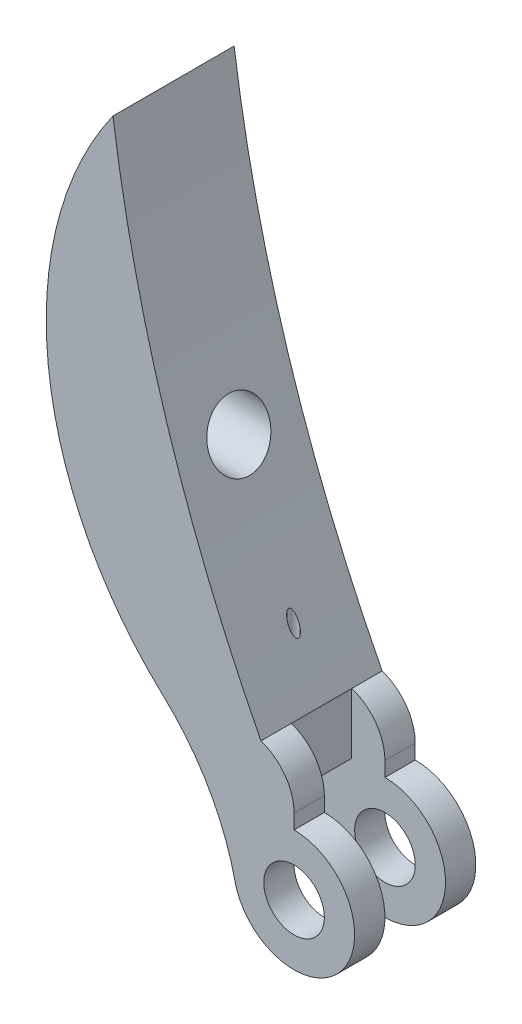
SolidWorks part; units mm, degrees
ref_plane "前视基准面" through (0, 0, 0) normal (0, 0, 1) x (1, 0, 0)
ref_plane "上视基准面" through (0, 0, 0) normal (0, 1, 0) x (1, 0, 0)
ref_plane "右视基准面" through (0, 0, 0) normal (1, 0, 0) x (0, 0, -1)
other "Configuration Table"
sketch "Sketch1" plane through (0, 0, 0) normal (0, 0, 1) x (1, 0, 0)
  line L0 (-2.5, 0) -> (-2.5, 5)
  line L1 (0, 0) -> (0, 5)
  line L2 (0, 5) -> (-2.5, 5)
  circle A0 centre (0, 0) radius 2.5
  circle A1 centre (0, 0) radius 1.25
  dimension "D1" = 2.5
  dimension "D2" = 5
  dimension "D3" = 5
extrude "Boss-Extrude1" add sketch "Sketch1" along normal blind 5 contours A0 L1 L2 L0 | A1 A0 region at (-1.7178, 1.7178, 0) region at (-1.3722, 3.4305, 0)
sketch "Sketch2" plane through (0, 0, 5) normal (0, 0, 1) x (1, 0, 0)
  line L0 (0, 2.5) -> (-2.5, 2.5) construction
  line L1 (0, 2.5) -> (0, 5) construction
  line L2 (-2.5, 0) -> (-2.5, 5) construction
  line L3 (0, 2.5) -> (4.7745, 15.618) construction
  line L4 (0, 2.5) -> (51.9615, 32.5) construction
  line L5 (0, 5) -> (0, 2.5) construction
  line L6 (-2.5, 2.5) -> (0, 2.5)
  arc A1 (-2.5, 0) -> (0, 2.5) centre (0, 0) ccw construction
  arc A2 (-2.5, 2.5) -> (-7.4726, 24.2787) centre (4.7745, 15.618) cw
  arc A3 (-7.4726, 24.2787) -> (0, 2.5) centre (51.9615, 32.5) ccw
  dimension "D1" = 60
  dimension "D2" = 15
  dimension "D3" = 20
  dimension "D4" = 40
extrude "Boss-Extrude2" add sketch "Sketch2" against normal blind 5
fillet "Fillet2" radius 10 1 edges at (-2.5, 2.5, 2.5)
sketch "Sketch4" plane through (0, 0, 0) normal (1, 0, 0) x (0, 0, -1)
  line L0 (-2.5, 5) -> (-2.5, 0) construction
  line L1 (-5, 5) -> (0, 5) construction
  line L3 (-3.75, -2.5) -> (-1.25, -2.5)
  line L4 (-3.75, -2.5) -> (-3.75, 2.5)
  line L5 (-3.75, 2.5) -> (-1.25, 2.5)
  line L6 (-1.25, -2.5) -> (-1.25, 2.5)
  line L7 (-3.75, -2.5) -> (-1.25, 2.5) construction
  line L8 (-3.75, 2.5) -> (-1.25, -2.5) construction
  dimension "D1" = 2.5
  dimension "D2" = 5
  dimension "D3" = 5
extrude "Cut-Extrude2" cut sketch "Sketch4" against normal through all both and the other way through all
sketch "Sketch5" plane through (0, 0, 0) normal (1, 0, 0) x (0, 0, -1)
  line L0 (-2.5, 5) -> (-2.5, 2.5) construction
  line L1 (0, 5) -> (-5, 5) construction
  line L2 (-3.75, 2.5) -> (-1.25, 2.5) construction
  line L3 (-2.5, 2.5) -> (-2.5, 3.75) construction
  line L4 (-5, 5) -> (0, 5) construction
  line L5 (-3.75, 2.5) -> (-1.25, 2.5)
  line L6 (-3.75, 2.5) -> (-3.75, 5)
  line L7 (-3.75, 5) -> (-1.25, 5)
  line L8 (-1.25, 2.5) -> (-1.25, 5)
  line L9 (-3.75, 2.5) -> (-1.25, 5) construction
  line L10 (-3.75, 5) -> (-1.25, 2.5) construction
  dimension "D1" = 2.5
extrude "Cut-Extrude3" cut sketch "Sketch5" against normal blind 1.37
fillet "Fillet3" radius 2 2 edges at (0, 5, 0.625) (0, 5, 4.375)
sketch "Sketch6" plane through (0, 0, 0) normal (1, 0, 0) x (0, 0, -1)
  line L2 (-1.25, 5) -> (-3.75, 5) construction
  line L3 (-2.5, 5) -> (-2.5, 13) construction
  circle A0 centre (-2.5, 13) radius 1.25
  dimension "D1" = 2.5
  dimension "D2" = 8
extrude "Cut-Extrude4" cut sketch "Sketch6" against normal through all
sketch "Sketch7" plane through (0, 2.5, 0) normal (0, -1, 0) x (1, 0, 0)
  line L0 (-3.6786, 2.5) -> (-1.3653, 2.5) construction
  line L1 (-3.6786, 1.25) -> (-3.6786, 3.75) construction
  line L2 (-1.3653, 1.25) -> (-1.3653, 3.75) construction
  line L3 (-2.522, 2.5) -> (-1.522, 2.5) construction
  circle A0 centre (-2.522, 2.5) radius 0.2
  dimension "D1" = 0.4
  dimension "D3" = 1
extrude "Cut-Extrude5" cut sketch "Sketch7" against normal through all
